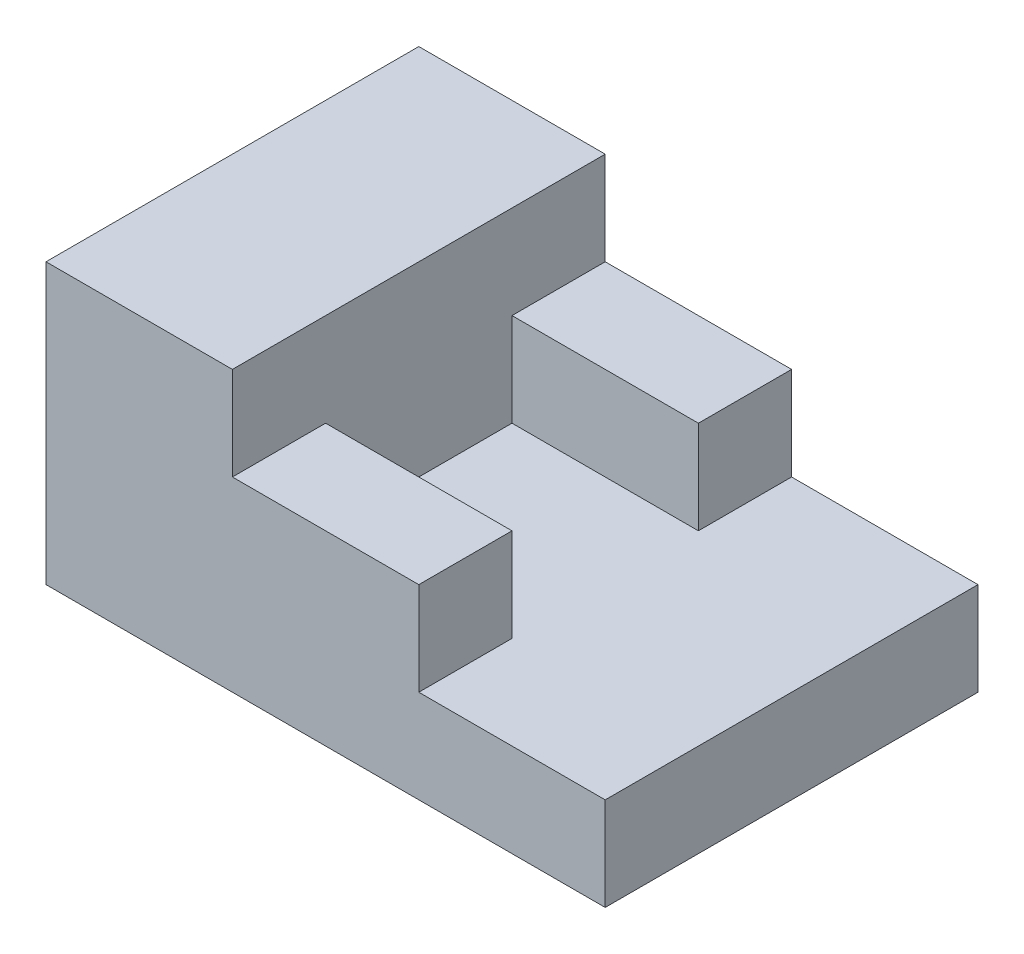
SolidWorks part; units mm, degrees
ref_plane "前基準面" through (0, 0, 0) normal (0, 0, 1) x (1, 0, 0)
ref_plane "上基準面" through (0, 0, 0) normal (0, 1, 0) x (1, 0, 0)
ref_plane "右基準面" through (0, 0, 0) normal (1, 0, 0) x (0, 0, -1)
sketch "草圖1" plane through (0, 0, 0) normal (0, 1, 0) x (1, 0, 0)
  line L0 (-5, 10) -> (-5, -10)
  line L1 (-15, -10) -> (15, -10)
  line L2 (-15, -10) -> (-15, 10)
  line L3 (-15, 10) -> (15, 10)
  line L4 (15, -10) -> (15, 10)
  line L5 (-15, -10) -> (15, 10) construction
  line L6 (-15, 10) -> (15, -10) construction
  line L7 (-5, -10) -> (-5, -5)
  line L8 (-5, -5) -> (5, -5)
  line L9 (5, -5) -> (5, -10)
  line L10 (-5, 5) -> (5, 5)
  line L11 (5, 5) -> (5, 10)
  point P0 (0, 0)
  point P13 (0, 0)
  dimension "D1" = 30
  dimension "D2" = 20
  dimension "D3" = 10
  dimension "D4" = 10
  dimension "D5" = 10
  dimension "D6" = 5
  dimension "D7" = 5
extrude "填料-伸長1" add sketch "草圖1" along normal blind 5 contours L11 L10 L0 L8 L9 L1 L4 L3 | L9 L8 L0 L1 | L3 L2 L1 L0 | L10 L11 L3 L0 region at (0, 0, -7.5) region at (-10, 0, 0) region at (6.6667, 0, 0) region at (0, 0, 7.5)
extrude "填料-伸長2" add sketch "草圖1<3>" along normal blind 10 contours L10 L11 L3 L0 | L9 L8 L0 L1 | L3 L2 L1 L0 region at (0, 0, -7.5) region at (-10, 0, 0) region at (0, 0, 7.5)
sketch "草圖1<3>" plane through (0, 0, 0) normal (0, 1, 0) x (1, 0, 0) same geometry as "草圖1"
extrude "填料-伸長3" add sketch "草圖1<4>" along normal blind 15 contours L3 L2 L1 L0 region at (-10, 0, 0)
sketch "草圖1<4>" plane through (0, 0, 0) normal (0, 1, 0) x (1, 0, 0) same geometry as "草圖1"
